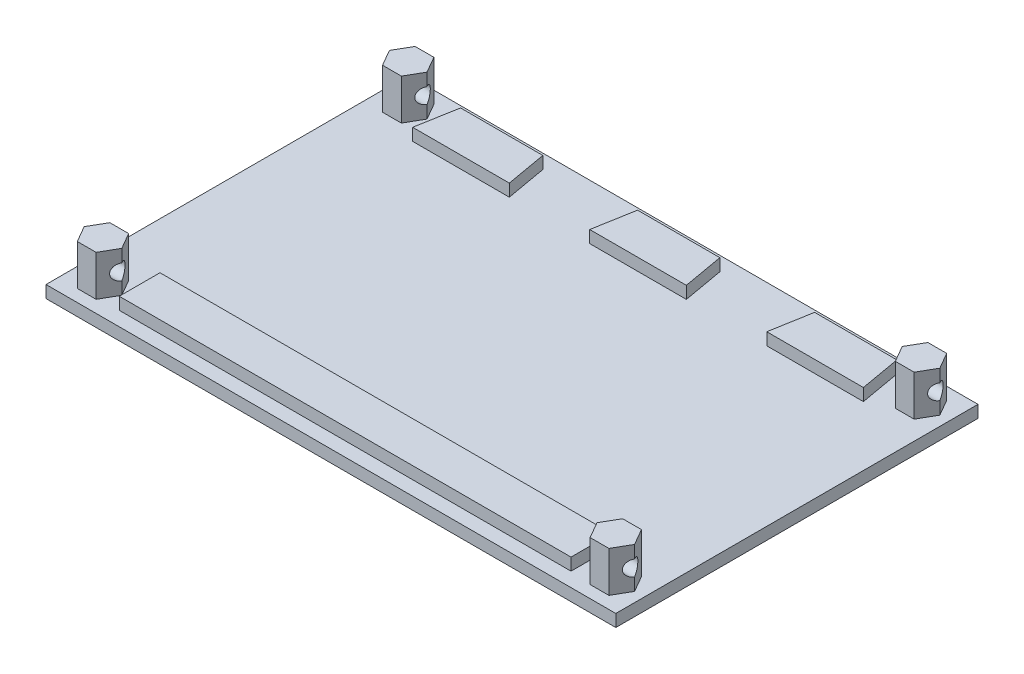
SolidWorks part; units mm, degrees
ref_plane "Front Plane" through (0, 0, 0) normal (0, 0, 1) x (1, 0, 0)
ref_plane "Top Plane" through (0, 0, 0) normal (0, 1, 0) x (1, 0, 0)
ref_plane "Right Plane" through (0, 0, 0) normal (1, 0, 0) x (0, 0, -1)
sketch "Sketch1" plane through (0, 0, 0) normal (0, 1, 0) x (1, 0, 0)
  line L0 (-53.4972, -7.3656) -> (86.5028, -7.3656)
  line L5 (86.5028, -7.3656) -> (86.5028, 47.6344)
  line L6 (86.5028, 47.6344) -> (-53.4972, 47.6344)
  line L7 (-53.4972, 47.6344) -> (-53.4972, -7.3656)
  line L8 (86.5028, 50.6344) -> (-53.4972, 50.6344)
  line L9 (-53.4972, -10.3656) -> (86.5028, -10.3656)
  line L10 (-53.4972, 47.6344) -> (-53.4972, 50.6344)
  line L11 (-53.4972, -10.3656) -> (-53.4972, -7.3656)
  line L12 (86.5028, -10.3656) -> (86.5028, -7.3656)
  line L13 (86.5028, 47.6344) -> (86.5028, 50.6344)
  line L14 (-53.4972, 20.1344) -> (86.5028, 20.1344) construction
  line L15 (-53.4972, 50.6344) -> (-53.4972, 64.6344)
  line L16 (-53.4972, 64.6344) -> (-39.4972, 64.6344)
  line L17 (-39.4972, 64.6344) -> (-39.4972, 50.6344)
  line L18 (-39.4972, 50.6344) -> (-53.4972, 50.6344)
  line L19 (-46.4972, 64.6344) -> (-46.4972, 50.6344) construction
  line L20 (-49.0953, -12.8656) -> (-43.8991, -12.8656)
  line L21 (-51.6934, 57.6344) -> (-41.3011, 57.6344) construction
  line L22 (-41.3011, 57.6344) -> (-43.8991, 62.1344)
  line L23 (-43.8991, 62.1344) -> (-49.0953, 62.1344)
  line L24 (-49.0953, 62.1344) -> (-51.6934, 57.6344)
  line L25 (-51.6934, 57.6344) -> (-49.0953, 53.1344)
  line L26 (-49.0953, 53.1344) -> (-43.8991, 53.1344)
  line L27 (-43.8991, 53.1344) -> (-41.3011, 57.6344)
  line L28 (-51.6934, -17.3656) -> (-41.3011, -17.3656) construction
  line L29 (-46.4972, -24.3656) -> (-46.4972, -10.3656) construction
  line L30 (-43.8991, -12.8656) -> (-41.3011, -17.3656)
  line L31 (-51.6934, -17.3656) -> (-49.0953, -12.8656)
  line L32 (-49.0953, -21.8656) -> (-51.6934, -17.3656)
  line L33 (-43.8991, -21.8656) -> (-49.0953, -21.8656)
  line L34 (-41.3011, -17.3656) -> (-43.8991, -21.8656)
  line L35 (-39.4972, -24.3656) -> (-39.4972, -10.3656)
  line L36 (-53.4972, -24.3656) -> (-39.4972, -24.3656)
  line L37 (-53.4972, -10.3656) -> (-53.4972, -24.3656)
  line L38 (16.5028, 47.6344) -> (16.5028, -7.3656) construction
  line L39 (-53.4972, -10.3656) -> (-39.4972, -10.3656)
  line L40 (79.5028, -24.3656) -> (79.5028, -10.3656) construction
  line L41 (84.6989, -17.3656) -> (74.3066, -17.3656) construction
  line L42 (86.5028, -10.3656) -> (86.5028, -24.3656)
  line L43 (86.5028, -24.3656) -> (72.5028, -24.3656)
  line L44 (72.5028, -24.3656) -> (72.5028, -10.3656)
  line L45 (74.3066, -17.3656) -> (76.9047, -21.8656)
  line L46 (76.9047, -21.8656) -> (82.1009, -21.8656)
  line L47 (82.1009, -21.8656) -> (84.6989, -17.3656)
  line L48 (84.6989, -17.3656) -> (82.1009, -12.8656)
  line L49 (76.9047, -12.8656) -> (74.3066, -17.3656)
  line L50 (82.1009, -12.8656) -> (76.9047, -12.8656)
  line L51 (86.5028, -10.3656) -> (72.5028, -10.3656)
  line L52 (82.1009, 53.1344) -> (76.9047, 53.1344)
  line L53 (84.6989, 57.6344) -> (74.3066, 57.6344) construction
  line L54 (79.5028, 64.6344) -> (79.5028, 50.6344) construction
  line L55 (76.9047, 53.1344) -> (74.3066, 57.6344)
  line L56 (84.6989, 57.6344) -> (82.1009, 53.1344)
  line L57 (82.1009, 62.1344) -> (84.6989, 57.6344)
  line L58 (76.9047, 62.1344) -> (82.1009, 62.1344)
  line L59 (74.3066, 57.6344) -> (76.9047, 62.1344)
  line L60 (72.5028, 64.6344) -> (72.5028, 50.6344)
  line L61 (86.5028, 64.6344) -> (72.5028, 64.6344)
  line L62 (86.5028, 50.6344) -> (86.5028, 64.6344)
  line L63 (-39.4972, 64.6344) -> (72.5028, 64.6344)
  line L64 (-39.4972, -24.3656) -> (72.5028, -24.3656)
  line L65 (-39.4972, 61.6344) -> (72.5028, 61.6344)
  line L66 (-39.4972, -21.3656) -> (72.5028, -21.3656)
  line L67 (-50.4972, 47.6344) -> (-50.4972, -7.3656)
  line L68 (-39.4972, 50.6344) -> (-37.0286, 64.6344)
  line L69 (-17.0286, 64.6344) -> (-14.5601, 50.6344)
  line L70 (72.5028, 50.6344) -> (70.0342, 64.6344)
  line L71 (50.0342, 64.6344) -> (47.5656, 50.6344)
  line L72 (4.0028, 50.6344) -> (6.4714, 64.6344)
  line L73 (26.4714, 64.6344) -> (28.9399, 50.6344)
  circle A0 centre (-46.4972, 57.6344) radius 4.5 construction
  circle A1 centre (-46.4972, -17.3656) radius 4.5 construction
  circle A2 centre (79.5028, -17.3656) radius 4.5 construction
  circle A3 centre (79.5028, 57.6344) radius 4.5 construction
  dimension "D5" = 9
  dimension "D1" = 55
  dimension "D2" = 140
  dimension "D3" = 14
  dimension "D4" = 14
  dimension "D6" = 3
  dimension "D7" = 3
  dimension "D8" = 80
  dimension "D9" = 80
  dimension "D10" = 20
sketch "Sketch2" plane through (0, 0, 0) normal (0, 1, 0) x (1, 0, 0)
  line L0 (-39.4972, 50.6344) -> (-37.5576, 61.6344) construction
  line L1 (-53.4972, 64.6344) -> (86.5028, 64.6344)
  line L2 (-53.4972, 64.6344) -> (-53.4972, -24.3656)
  line L3 (-53.4972, -24.3656) -> (86.5028, -24.3656)
  line L4 (86.5028, 64.6344) -> (86.5028, -24.3656)
  line L5 (-39.4972, -10.3656) -> (72.5028, -10.3656) construction
  line L6 (-39.4972, -10.3656) -> (-39.4972, -21.3656) construction
  line L7 (-39.4972, -21.3656) -> (72.5028, -21.3656) construction
  line L8 (72.5028, -10.3656) -> (72.5028, -21.3656) construction
  line L9 (-39.4972, 61.6344) -> (72.5028, 61.6344) construction
  line L10 (-39.4972, 50.6344) -> (-37.0286, 64.6344) construction
  line L11 (-37.5576, 61.6344) -> (-16.4997, 61.6344) construction
  line L12 (-17.0286, 64.6344) -> (-14.5601, 50.6344) construction
  line L13 (-16.4997, 61.6344) -> (-14.5601, 50.6344) construction
  line L14 (-14.5601, 50.6344) -> (-39.4972, 50.6344) construction
  line L15 (27.0003, 61.6344) -> (28.9399, 50.6344) construction
  line L16 (28.9399, 50.6344) -> (4.0028, 50.6344) construction
  line L17 (4.0028, 50.6344) -> (5.9424, 61.6344) construction
  line L18 (5.9424, 61.6344) -> (27.0003, 61.6344) construction
  line L19 (70.5003, 61.6344) -> (72.4399, 50.6344) construction
  line L20 (72.4399, 50.6344) -> (47.5028, 50.6344) construction
  line L21 (47.5028, 50.6344) -> (49.4424, 61.6344) construction
  line L22 (49.4424, 61.6344) -> (70.5003, 61.6344) construction
  line L23 (84.6989, 57.6344) -> (74.3066, 57.6344) construction
  line L24 (-43.8991, 62.1344) -> (-49.0953, 62.1344) construction
  line L25 (-49.0953, 62.1344) -> (-51.6934, 57.6344) construction
  line L26 (-51.6934, 57.6344) -> (-49.0953, 53.1344) construction
  line L27 (-49.0953, 53.1344) -> (-43.8991, 53.1344) construction
  line L28 (-43.8991, 53.1344) -> (-41.3011, 57.6344) construction
  line L29 (-41.3011, 57.6344) -> (-43.8991, 62.1344) construction
  line L30 (82.1009, 62.1344) -> (76.9047, 62.1344) construction
  line L31 (76.9047, 62.1344) -> (74.3066, 57.6344) construction
  line L32 (74.3066, 57.6344) -> (76.9047, 53.1344) construction
  line L33 (76.9047, 53.1344) -> (82.1009, 53.1344) construction
  line L34 (82.1009, 53.1344) -> (84.6989, 57.6344) construction
  line L35 (84.6989, 57.6344) -> (82.1009, 62.1344) construction
  line L36 (-51.6934, -17.3656) -> (-41.3011, -17.3656) construction
  line L37 (82.1009, -12.8656) -> (76.9047, -12.8656) construction
  line L38 (76.9047, -12.8656) -> (74.3066, -17.3656) construction
  line L39 (74.3066, -17.3656) -> (76.9047, -21.8656) construction
  line L40 (76.9047, -21.8656) -> (82.1009, -21.8656) construction
  line L41 (82.1009, -21.8656) -> (84.6989, -17.3656) construction
  line L42 (84.6989, -17.3656) -> (82.1009, -12.8656) construction
  line L43 (-43.8991, -12.8656) -> (-49.0953, -12.8656) construction
  line L44 (-49.0953, -12.8656) -> (-51.6934, -17.3656) construction
  line L45 (-51.6934, -17.3656) -> (-49.0953, -21.8656) construction
  line L46 (-49.0953, -21.8656) -> (-43.8991, -21.8656) construction
  line L47 (-43.8991, -21.8656) -> (-41.3011, -17.3656) construction
  line L48 (-41.3011, -17.3656) -> (-43.8991, -12.8656) construction
  line L49 (-37.1381, 61.1344) -> (-16.9192, 61.1344)
  line L50 (-16.9192, 61.1344) -> (-15.1559, 51.1344)
  line L51 (-15.1559, 51.1344) -> (-38.9013, 51.1344)
  line L52 (-38.9013, 51.1344) -> (-37.1381, 61.1344)
  line L53 (28.3441, 51.1344) -> (4.5987, 51.1344)
  line L54 (4.5987, 51.1344) -> (6.3619, 61.1344)
  line L55 (6.3619, 61.1344) -> (26.5808, 61.1344)
  line L56 (26.5808, 61.1344) -> (28.3441, 51.1344)
  line L57 (71.8441, 51.1344) -> (48.0987, 51.1344)
  line L58 (48.0987, 51.1344) -> (49.8619, 61.1344)
  line L59 (49.8619, 61.1344) -> (70.0808, 61.1344)
  line L60 (70.0808, 61.1344) -> (71.8441, 51.1344)
  line L61 (-38.9972, -20.8656) -> (72.0028, -20.8656)
  line L62 (72.0028, -10.8656) -> (72.0028, -20.8656)
  line L63 (-38.9972, -10.8656) -> (72.0028, -10.8656)
  line L64 (-38.9972, -10.8656) -> (-38.9972, -20.8656)
  line L65 (-44.1878, -13.3656) -> (-48.8066, -13.3656)
  line L66 (-48.8066, -13.3656) -> (-51.116, -17.3656)
  line L67 (-51.116, -17.3656) -> (-48.8066, -21.3656)
  line L68 (-48.8066, -21.3656) -> (-44.1878, -21.3656)
  line L69 (-44.1878, -21.3656) -> (-41.8784, -17.3656)
  line L70 (-41.8784, -17.3656) -> (-44.1878, -13.3656)
  line L71 (-48.8066, 53.6344) -> (-44.1878, 53.6344)
  line L72 (-44.1878, 53.6344) -> (-41.8784, 57.6344)
  line L73 (-41.8784, 57.6344) -> (-44.1878, 61.6344)
  line L74 (-44.1878, 61.6344) -> (-48.8066, 61.6344)
  line L75 (-48.8066, 61.6344) -> (-51.116, 57.6344)
  line L76 (-51.116, 57.6344) -> (-48.8066, 53.6344)
  line L77 (74.884, 57.6344) -> (77.1934, 53.6344)
  line L78 (77.1934, 53.6344) -> (81.8122, 53.6344)
  line L79 (81.8122, 53.6344) -> (84.1216, 57.6344)
  line L80 (84.1216, 57.6344) -> (81.8122, 61.6344)
  line L81 (81.8122, 61.6344) -> (77.1934, 61.6344)
  line L82 (77.1934, 61.6344) -> (74.884, 57.6344)
  line L83 (81.8122, -21.3656) -> (84.1216, -17.3656)
  line L84 (84.1216, -17.3656) -> (81.8122, -13.3656)
  line L85 (81.8122, -13.3656) -> (77.1934, -13.3656)
  line L86 (77.1934, -13.3656) -> (74.884, -17.3656)
  line L87 (74.884, -17.3656) -> (77.1934, -21.3656)
  line L88 (77.1934, -21.3656) -> (81.8122, -21.3656)
  circle A0 centre (-46.4972, 57.6344) radius 4.5 construction
  circle A1 centre (79.5028, 57.6344) radius 4.5 construction
  circle A2 centre (79.5028, -17.3656) radius 4.5 construction
  circle A3 centre (-46.4972, -17.3656) radius 4.5 construction
  dimension "D2" = 0.5
  dimension "D4" = 0.5
  dimension "D5" = 0.5
  dimension "D6" = 0.5
  dimension "D7" = 0.5
  dimension "D8" = 0.5
  dimension "D1" = 3
  dimension "D3" = 3
sketch "Sketch3" plane through (0, 0, 0) normal (0, 1, 0) x (1, 0, 0)
  line L1 (-53.4972, 64.6344) -> (86.5028, 64.6344)
  line L2 (-53.4972, 64.6344) -> (-53.4972, -24.3656)
  line L3 (-53.4972, -24.3656) -> (86.5028, -24.3656)
  line L4 (86.5028, 64.6344) -> (86.5028, -24.3656)
extrude "Boss-Extrude1" add sketch "Sketch3" against normal blind 3
extrude "Boss-Extrude3" add sketch "Sketch2" along normal blind 3 contours L52 L51 L50 L49 | L56 L55 L54 L53 | L60 L59 L58 L57 | L63 L64 L61 L62 region at (-27.0286, 0, -56.0007) region at (16.4714, 0, -56.0007) region at (59.9714, 0, -56.0007) region at (16.5028, 0, 15.8656)
extrude "Boss-Extrude4" add sketch "Sketch2<4>" along normal blind 10 contours L69 L70 L65 L66 L67 L68 | L72 L73 L74 L75 L76 L71 | L79 L80 L81 L82 L77 L78 | L83 L84 L85 L86 L87 L88
sketch "Sketch2<4>" plane through (0, 0, 0) normal (0, 1, 0) x (1, 0, 0) same geometry as "Sketch2"
sketch "Sketch4" plane through (-53.4972, 0, 0) normal (-1, 0, 0) x (0, 0, 1)
  line L0 (-64.6344, -3) -> (-64.6344, 5) construction
  line L1 (-64.6344, 5) -> (-50.6344, 5) construction
  line L4 (-20.1344, -3) -> (-20.1344, 36.4957) construction
  circle A0 centre (-57.6344, 5) radius 1.9
  circle A1 centre (17.3656, 5) radius 1.9
  dimension "D3" = 3.8
  dimension "D1" = 14
  dimension "D2" = 8
extrude "Cut-Extrude1" cut sketch "Sketch4" against normal through all
